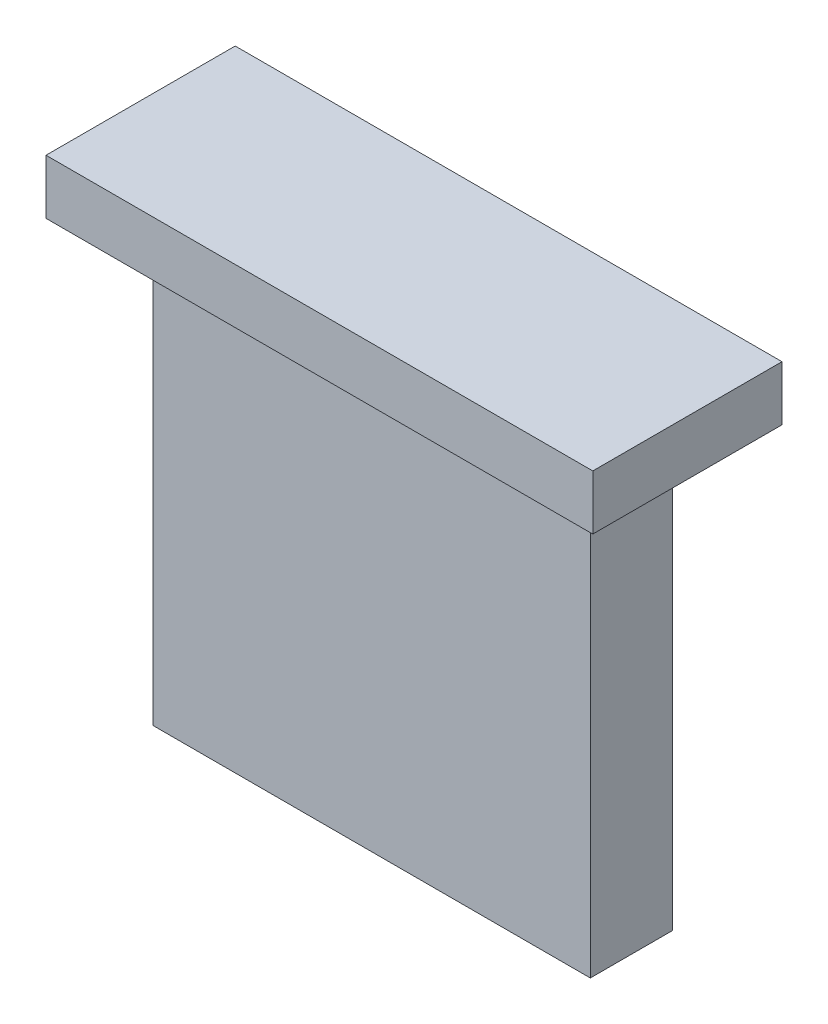
SolidWorks part; units mm, degrees
ref_plane "Front Plane" through (0, 0, 0) normal (0, 0, 1) x (1, 0, 0)
ref_plane "Top Plane" through (0, 0, 0) normal (0, 1, 0) x (1, 0, 0)
ref_plane "Right Plane" through (0, 0, 0) normal (1, 0, 0) x (0, 0, -1)
sketch "Sketch1" plane through (0, 0, 0) normal (0, 1, 0) x (1, 0, 0)
  line L1 (0, 0) -> (8, 0)
  line L2 (0, 0) -> (0, 1.5)
  line L3 (0, 1.5) -> (8, 1.5)
  line L4 (8, 0) -> (8, 1.5)
extrude "Boss-Extrude1" add sketch "Sketch1" along normal blind 8
sketch "Sketch2" plane through (0, 8, 0) normal (0, 1, 0) x (1, 0, 0)
  line L0 (0, 1.5) -> (0, 2.5)
  line L1 (0, 1.5) -> (-1.0091, 1.5)
  line L2 (-1.0091, 1.5) -> (-1.0091, 2.5143)
  line L4 (-1.0091, 2.5143) -> (8.9909, 2.5143)
  line L5 (-1.0091, 2.5143) -> (-1.0091, -0.9461)
  line L6 (-1.0091, -0.9461) -> (8.9909, -0.9461)
  line L7 (8.9909, 2.5143) -> (8.9909, -0.9461)
  line M7 (0, 1.5) -> (0, 0)
  line M8 (0, 0) -> (8, 0)
  line M9 (8, 0) -> (8, 1.5)
  line M10 (8, 1.5) -> (0, 1.5)
extrude "Boss-Extrude2" add sketch "Sketch2" along normal blind 1 contours L7 L4 L2 L5 L6 | M10 M7 M8 M9 region at (-0.9032, 8, -2.0072) region at (4, 8, -0.75)
